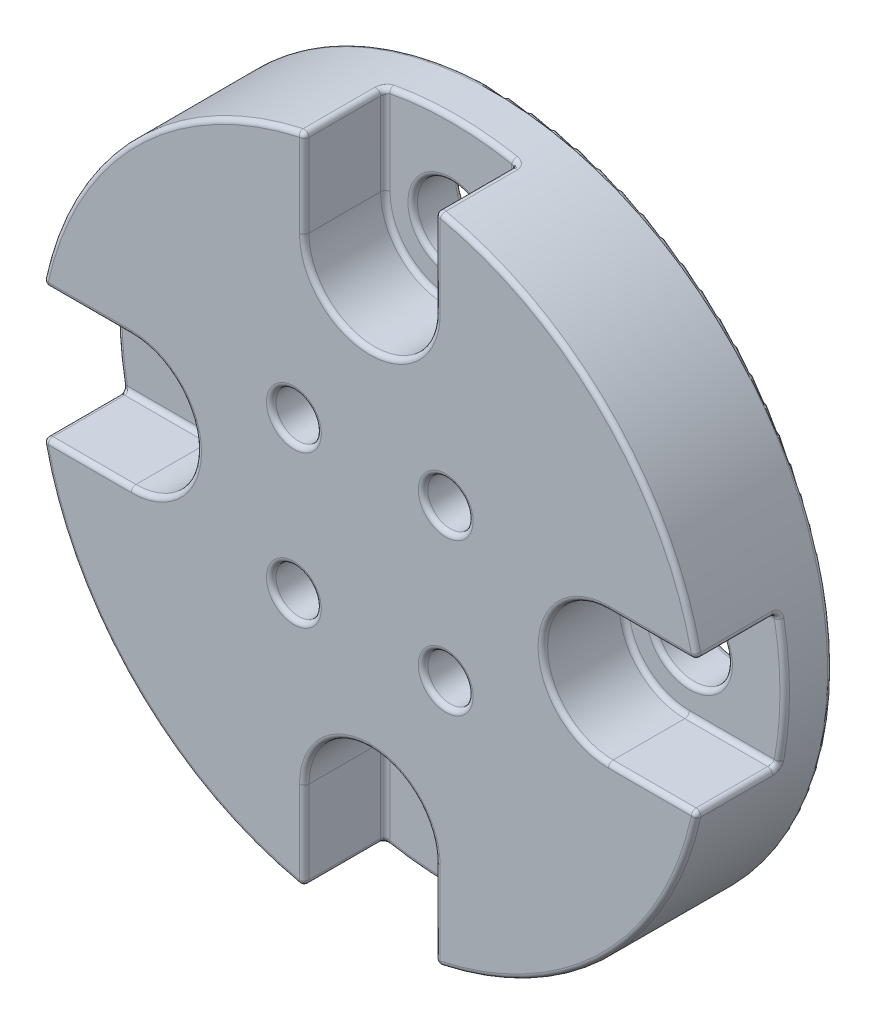
SolidWorks part; units mm, degrees
ref_plane "정면" through (0, 0, 0) normal (0, 0, 1) x (1, 0, 0)
ref_plane "윗면" through (0, 0, 0) normal (0, 1, 0) x (1, 0, 0)
ref_plane "우측면" through (0, 0, 0) normal (1, 0, 0) x (0, 0, -1)
sketch "스케치1" plane through (0, 0, 0) normal (0, 0, 1) x (1, 0, 0)
  circle A0 centre (0, 0) radius 15
  circle A1 centre (0, 0) radius 11.5
  dimension "D1" = 23
  dimension "D2" = 30
extrude "보스-돌출1" add sketch "스케치1" against normal blind 1.8 contours A0 A1 region at (-14.5757, 0, 0)
extrude "보스-돌출2" add sketch "스케치1<3>" along normal blind 2 contours A0 A1 | A1 region at (-14.5757, 0, 0)
sketch "스케치1<3>" plane through (0, 0, 0) normal (0, 0, 1) x (1, 0, 0) same geometry as "스케치1"
sketch "스케치2" plane through (0, 0, 2) normal (0, 0, 1) x (1, 0, 0)
  circle A0 centre (0, 10.005) radius 1.6
  circle A1 centre (10.005, 0) radius 1.6
  circle A2 centre (0, -10.005) radius 1.6
  circle A3 centre (-10.005, 0) radius 1.6
  point P12 (0, 0)
  dimension "D1" = 3.2
  dimension "D2" = 10.005
  dimension "D3" = 4
extrude "컷-돌출1" cut sketch "스케치2" against normal blind 2
sketch "스케치3" plane through (0, 0, 2) normal (0, 0, 1) x (1, 0, 0)
  line L0 (-10.005, 2.75) -> (-14.7458, 2.75)
  line L1 (-10.005, -2.75) -> (-14.7458, -2.75)
  line L2 (10.005, 2.75) -> (14.7458, 2.75)
  line L3 (10.005, -2.75) -> (14.7458, -2.75)
  line L4 (2.75, 10.005) -> (2.75, 14.7458)
  line L5 (-2.75, 10.005) -> (-2.75, 14.7458)
  line L6 (2.75, -10.005) -> (2.75, -14.7458)
  line L7 (-2.75, -10.005) -> (-2.75, -14.7458)
  arc A0 (-10.005, -2.75) -> (-10.005, 2.75) centre (-10.005, 0) ccw
  arc A1 (-2.75, 10.005) -> (2.75, 10.005) centre (0, 10.005) ccw
  arc A2 (10.005, 2.75) -> (10.005, -2.75) centre (10.005, 0) ccw
  arc A3 (2.75, -10.005) -> (-2.75, -10.005) centre (0, -10.005) ccw
  arc A4 (14.7458, 2.75) -> (2.75, 14.7458) centre (0, 0) ccw
  circle A5 centre (0, 0) radius 15
  arc A6 (-2.75, 14.7458) -> (-14.7458, 2.75) centre (0, 0) ccw
  arc A7 (-14.7458, -2.75) -> (-2.75, -14.7458) centre (0, 0) ccw
  arc A8 (2.75, -14.7458) -> (14.7458, -2.75) centre (0, 0) ccw
  dimension "D1" = 5.5
  dimension "D2" = 0
extrude "보스-돌출3" add sketch "스케치3" along normal blind 3.4 contours A1 L4 A4 L2 A2 L3 A8 L6 A3 L7 A7 L1 A0 L0 A6 L5
sketch "스케치4" plane through (0, 0, 5.4) normal (0, 0, 1) x (1, 0, 0)
  line L0 (0, 0) -> (16.9927, 0) construction
  line L1 (0, 0) -> (3.182, 3.182) construction
  circle A0 centre (3.182, 3.182) radius 0.95
  circle A1 centre (3.182, -3.182) radius 0.95
  circle A2 centre (-3.182, -3.182) radius 0.95
  circle A3 centre (-3.182, 3.182) radius 0.95
  point P14 (0, 0)
  dimension "D3" = 1.9
  dimension "D1" = 45
  dimension "D2" = 4.5
  dimension "D4" = 4
extrude "컷-돌출2" cut sketch "스케치4" against normal through all
sketch "스케치5" plane through (0, 0, 5.4) normal (0, 0, 1) x (1, 0, 0)
  circle A0 centre (0, 0) radius 14
  circle A1 centre (0, 0) radius 30.1031
  line M5 (-2.75, 10.005) -> (-2.75, 14.7458)
  arc M6 (-2.75, 14.7458) -> (-14.7458, 2.75) centre (0, 0) ccw
  line M7 (-14.7458, 2.75) -> (-10.005, 2.75)
  line M9 (-10.005, -2.75) -> (-14.7458, -2.75)
  arc M10 (-14.7458, -2.75) -> (-2.75, -14.7458) centre (0, 0) ccw
  line M11 (-2.75, -14.7458) -> (-2.75, -10.005)
  line M13 (2.75, -10.005) -> (2.75, -14.7458)
  arc M14 (2.75, -14.7458) -> (14.7458, -2.75) centre (0, 0) ccw
  line M15 (14.7458, -2.75) -> (10.005, -2.75)
  line M17 (10.005, 2.75) -> (14.7458, 2.75)
  arc M18 (14.7458, 2.75) -> (2.75, 14.7458) centre (0, 0) ccw
  line M19 (2.75, 14.7458) -> (2.75, 10.005)
  dimension "D1" = 28
extrude "컷-돌출3" cut sketch "스케치5" against normal through all contours A1 A0 M19 M18 M17 M15 M14 M13 M11 M10 M9 M7 M6 M5 | A0 M9 M10 M11 | A0 M5 M6 M7 | A0 M17 M18 M19 | A0 M13 M14 M15 region at (10.0195, 10.0195, 5.4) region at (14.2365, -2.9196, 5.4) region at (-10.0195, 10.0195, 5.4) region at (-2.9196, -14.2365, 5.4) region at (-29.2516, 0, 5.4)
sketch "스케치6" plane through (0, 0, 0) normal (0, 0, -1) x (-1, 0, 0)
  circle A0 centre (0, 0) radius 28.4306
extrude "컷-돌출4" cut sketch "스케치6" along normal blind 10
fillet "필렛1" radius 0.2 57 edges at (-2.75, 13.7273, 3.7) (2.75, 13.7273, 3.7) (-13.7273, -2.75, 3.7) (-13.7273, 2.75, 3.7) (2.75, -13.7273, 3.7) (-2.75, -13.7273, 3.7) (13.7273, 2.75, 3.7) (13.7273, -2.75, 3.7) (0, 7.255, 2) (-2.75, 11.8661, 2) (0, 14, 2) (2.75, 11.8661, 2) (1.6, 10.005, 2) (-7.255, 0, 2) (-11.8661, -2.75, 2) (-14, 0, 2) (-11.8661, 2.75, 2) (-8.405, 0, 2) (0, -7.255, 2) (2.75, -11.8661, 2) (0, -14, 2) (-2.75, -11.8661, 2) (1.6, -10.005, 2) (7.255, 0, 2) (11.8661, 2.75, 2) (14, 0, 2) (11.8661, -2.75, 2) (11.605, 0, 2) (-14, 0, 0) (-8.405, 0, 0) (4.132, 3.182, 0) (4.132, -3.182, 0) (-2.232, -3.182, 0) (-2.232, 3.182, 0) (1.6, 10.005, 0) (11.605, 0, 0) (1.6, -10.005, 0) (7.255, 0, 5.4) (11.8661, -2.75, 5.4) (9.8995, -9.8995, 5.4) (2.75, -11.8661, 5.4) (0, -7.255, 5.4) (-2.75, -11.8661, 5.4) (-9.8995, -9.8995, 5.4) (-11.8661, -2.75, 5.4) (-7.255, 0, 5.4) (-11.8661, 2.75, 5.4) (-9.8995, 9.8995, 5.4) (-2.75, 11.8661, 5.4) (0, 7.255, 5.4) (2.75, 11.8661, 5.4) (9.8995, 9.8995, 5.4) (11.8661, 2.75, 5.4) (4.132, 3.182, 5.4) (4.132, -3.182, 5.4) (-2.232, -3.182, 5.4) (-2.232, 3.182, 5.4)
